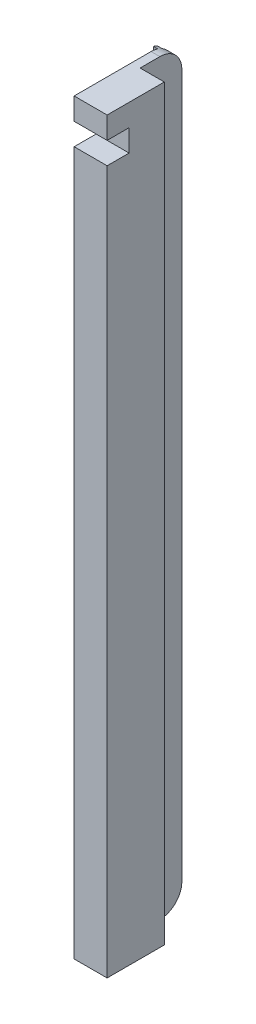
SolidWorks part; units mm, degrees
ref_plane "정면" through (0, 0, 0) normal (0, 0, 1) x (1, 0, 0)
ref_plane "윗면" through (0, 0, 0) normal (0, 1, 0) x (1, 0, 0)
ref_plane "우측면" through (0, 0, 0) normal (1, 0, 0) x (0, 0, -1)
sketch "스케치1" plane through (0, 0, 0) normal (0, 0, 1) x (1, 0, 0)
  line L0 (-318.5049, 0) -> (318.5049, 0) construction
  line L1 (0, 0) -> (0, -258.8265) construction
  line L2 (-168, 0) -> (168, 0)
  line L3 (-168, -20) -> (168, -20)
  line L4 (168, -20) -> (168, 0) construction
  line L5 (168, -20) -> (168, -340)
  line L6 (172, -340) -> (172, 0)
  line L7 (168, 0) -> (183, 0)
  line L8 (183, 0) -> (183, -340)
  line L9 (183, -340) -> (168, -340)
  line L10 (-168, -20) -> (-168, 0) construction
  line L11 (-183, -340) -> (-168, -340)
  line L12 (-183, 0) -> (-183, -340)
  line L13 (-168, 0) -> (-183, 0)
  line L14 (-172, -340) -> (-172, 0)
  line L15 (-168, -20) -> (-168, -340)
  line L16 (168, -20) -> (168, 0)
  line L17 (-168, -20) -> (-168, 0)
  point P14 (0, -20)
  dimension "D1" = 168
  dimension "D2" = 20
  dimension "D3" = 4
  dimension "D4" = 340
  dimension "D5" = 15
extrude "보스-돌출1" add sketch "스케치1" along normal blind 26 contours L3 L5 L9 L8 L7 L2 L13 L12 L11 L15
extrude "보스-돌출2" add sketch "스케치1<4>" against normal blind 19 contours L16 L5 L9 L6 L7 | L15 L17 L13 L14 L11 region at (-170, -170, 0) region at (170, -170, 0)
sketch "스케치1<4>" plane through (0, 0, 0) normal (0, 0, 1) x (1, 0, 0) same geometry as "스케치1"
fillet "필렛1" radius 10 4 edges at (-170, 0, -19) (170, 0, -19) (170, -340, -19) (-170, -340, -19)
sketch "스케치2" plane through (172, 0, 0) normal (1, 0, 0) x (0, 0, -1)
  line L0 (14, -340) -> (14, 0)
  line L1 (12, 0) -> (12, -340)
  line L4 (19, -330) -> (19, -10)
  line L5 (9, 0) -> (0, 0)
  line L6 (0, 0) -> (0, -340)
  line L7 (0, -340) -> (9, -340)
  line L8 (19, -330) -> (19, -10)
  line L9 (9, 0) -> (0, 0)
  line L10 (0, 0) -> (0, -340)
  line L11 (0, -340) -> (9, -340)
  arc A2 (19, -10) -> (9, 0) centre (9, -10) ccw
  arc A3 (9, -340) -> (19, -330) centre (9, -330) ccw
  arc A4 (19, -10) -> (9, 0) centre (9, -10) ccw
  arc A5 (9, -340) -> (19, -330) centre (9, -330) ccw
  dimension "D2" = 5
  dimension "D3" = 2
  dimension "D1" = 0
sketch "스케치3" plane through (168, 0, 0) normal (-1, 0, 0) x (0, 0, 1)
  line L0 (-12, 0) -> (-12, -340) construction
  line L1 (-14, -340) -> (-14, 0) construction
  line L2 (-12, 0) -> (-12, -340)
  line L3 (-14, -340) -> (-14, 0)
  line L4 (-19, -10) -> (-19, -330)
  line L5 (0, 0) -> (-9, 0)
  line L6 (0, -340) -> (0, 0)
  line L7 (-9, -340) -> (0, -340)
  line L8 (-19, -10) -> (-19, -330)
  line L9 (0, 0) -> (-9, 0)
  line L10 (0, -340) -> (0, 0)
  line L11 (-9, -340) -> (0, -340)
  arc A2 (-9, 0) -> (-19, -10) centre (-9, -10) ccw
  arc A3 (-19, -330) -> (-9, -340) centre (-9, -330) ccw
  arc A4 (-9, 0) -> (-19, -10) centre (-9, -10) ccw
  arc A5 (-19, -330) -> (-9, -340) centre (-9, -330) ccw
  arc M8 (-9, 0) -> (-19, -10) centre (-9, -10) ccw
  arc M10 (-19, -330) -> (-9, -340) centre (-9, -330) ccw
  dimension "D1" = 0
extrude "보스-돌출3" add sketch "스케치3" along normal blind 2 contours L3 L2 M10 M8 region at (168, -170, -12.9991)
mirror "대칭 복사1" about plane through (0, 0, 0) normal (1, 0, 0) of "보스-돌출3"
sketch "스케치5" plane through (0, 0, 0) normal (0, 1, 0) x (1, 0, 0)
  line L0 (-7, 0) -> (-7, -26)
  line L1 (7, 0) -> (7, -26)
  line L2 (-168, 0) -> (-168, -6)
  line L3 (-168, -6) -> (-7, -6)
  line L4 (7, -6) -> (168, -6)
  line L5 (168, -6) -> (168, 0)
  line L12 (-168, 0) -> (-168, 9)
  line L13 (-168, 9) -> (-172, 9)
  line L14 (-172, 9) -> (-172, 0)
  line L15 (-172, 0) -> (-183, 0)
  line L16 (-183, 0) -> (-183, -26)
  line L17 (-183, -26) -> (183, -26)
  line L18 (183, -26) -> (183, 0)
  line L19 (183, 0) -> (172, 0)
  line L20 (172, 0) -> (172, 9)
  line L21 (172, 9) -> (168, 9)
  line L22 (168, 9) -> (168, 0)
  line L23 (168, 0) -> (-168, 0)
  line L24 (-168, 0) -> (-168, 9)
  line L25 (-168, 9) -> (-172, 9)
  line L26 (-172, 9) -> (-172, 0)
  line L27 (-172, 0) -> (-183, 0)
  line L28 (-183, 0) -> (-183, -26)
  line L29 (-183, -26) -> (183, -26)
  line L30 (183, -26) -> (183, 0)
  line L31 (183, 0) -> (172, 0)
  line L32 (172, 0) -> (172, 9)
  line L33 (172, 9) -> (168, 9)
  line L34 (168, 9) -> (168, 0)
  line L35 (168, 0) -> (-168, 0)
  line M27 (168, 0) -> (-168, 0)
  dimension "D2" = 7
  dimension "D3" = 7
  dimension "D4" = 6
  dimension "D1" = 0
extrude "컷-돌출1" cut sketch "스케치5" against normal blind 52 contours L2 L3 L0 M27 | L4 L5 L1 M27 region at (-87.5, 0, 3) region at (87.5, 0, 3)
sketch "스케치6" plane through (168, 0, 0) normal (-1, 0, 0) x (0, 0, 1)
  line L0 (26, -20) -> (26, -340) construction
  line L1 (-71.7494, 105.886) -> (84.6976, 105.886)
  line L2 (-71.7494, 105.886) -> (-71.7494, -374.2228)
  line L3 (-71.7494, -374.2228) -> (84.6976, -374.2228)
  line L4 (84.6976, 105.886) -> (84.6976, -374.2228)
  line L5 (-71.7494, 105.886) -> (84.6976, -374.2228) construction
  line L6 (-71.7494, -374.2228) -> (84.6976, 105.886) construction
  line L7 (26, -340) -> (0, -340) construction
  line L8 (26, 0) -> (6, 0)
  line L9 (-9, 0) -> (6, 0)
  line L10 (-9, 0) -> (6, 0)
  line L11 (26, 0) -> (6, 0)
  line L12 (26, -20) -> (26, -340)
  line L13 (26, -20) -> (26, 0)
  line L14 (26, -20) -> (26, 0)
  line L15 (26, -20) -> (26, -340)
  line L16 (26, -20) -> (6, -20)
  line L17 (26, -20) -> (6, -20)
  line L18 (6, -20) -> (6, 0)
  line L19 (6, -20) -> (6, 0)
  point P0 (6.4741, -134.1684)
  line M5 (26, -20) -> (6, -20)
  line M6 (6, -20) -> (6, 0)
  line M7 (6, 0) -> (-9, 0)
  arc M8 (-9, 0) -> (-12, -0.4606) centre (-9, -10) ccw
  line M9 (-12, -0.4606) -> (-12, -339.5394)
  arc M10 (-12, -339.5394) -> (-9, -340) centre (-9, -330) ccw
  line M11 (-9, -340) -> (26, -340)
  line M12 (26, -340) -> (26, -20)
  dimension "D1" = 19.5259
  dimension "D2" = 240.0544
  dimension "D3" = 156.447
  dimension "D4" = 205.8316
extrude "컷-돌출3" cut sketch "스케치6" along normal blind 401 contours L4 L1 L2 L3 L14 L11 M12 M11 M10 M9 M8 M7 | L14 L11 M5 M6 | M12 M5 M6 M7 M8 M9 M10 M11 region at (168, 100.8364, 6.4741) region at (168, -10, 16) region at (168, -175.1122, 6.7138)
sketch "스케치7" plane through (168, 0, 0) normal (-1, 0, 0) x (0, 0, 1)
  line L0 (26, -20) -> (26, -340) construction
  line L1 (26, 0) -> (6, 0) construction
  line L2 (26, -20) -> (26, 0) construction
  line L3 (26, -20) -> (6, -20) construction
  line L4 (26, -340) -> (26, 0)
  line L5 (26, 0) -> (-9, 0)
  line L6 (-19, -10) -> (-19, -330)
  line L7 (-9, -340) -> (26, -340)
  line L8 (26, -340) -> (26, 0)
  line L9 (26, 0) -> (-9, 0)
  line L10 (-19, -10) -> (-19, -330)
  line L11 (-9, -340) -> (26, -340)
  line L12 (6, -20) -> (6, 0) construction
  line L13 (-9, 0) -> (6, 0) construction
  line L14 (-71.7494, 105.886) -> (84.6976, 105.886) construction
  line L15 (84.6976, 105.886) -> (84.6976, -374.2228) construction
  line L16 (-71.7494, -374.2228) -> (84.6976, -374.2228) construction
  line L17 (-71.7494, 105.886) -> (-71.7494, -374.2228) construction
  line L18 (26, -20) -> (26, -340)
  line L19 (26, 0) -> (6, 0)
  line L20 (26, -20) -> (26, 0)
  line L21 (26, -20) -> (6, -20)
  line L22 (6, -20) -> (6, 0)
  line L23 (-9, 0) -> (6, 0)
  line L24 (-71.7494, 105.886) -> (84.6976, 105.886)
  line L25 (84.6976, 105.886) -> (84.6976, -374.2228)
  line L26 (-71.7494, -374.2228) -> (84.6976, -374.2228)
  line L27 (-71.7494, 105.886) -> (-71.7494, -374.2228)
  line L29 (16, -10) -> (26, -10)
  line L30 (16, -10) -> (16, -20)
  line L31 (16, -20) -> (26, -20)
  line L32 (26, -10) -> (26, -20)
  line L33 (16, -10) -> (26, -20) construction
  line L34 (16, -20) -> (26, -10) construction
  arc A2 (-9, 0) -> (-19, -10) centre (-9, -10) ccw
  arc A3 (-19, -330) -> (-9, -340) centre (-9, -330) ccw
  arc A4 (-9, 0) -> (-19, -10) centre (-9, -10) ccw
  arc A5 (-19, -330) -> (-9, -340) centre (-9, -330) ccw
  point P15 (21, -15)
  dimension "D2" = 10
  dimension "D3" = 10
  dimension "D4" = 0
  dimension "D1" = 0
extrude "컷-돌출4" cut sketch "스케치7" against normal blind 401 contours L29 L30 L21 L8 region at (168, -15, 21)
sketch "스케치8" plane through (168, 0, 0) normal (-1, 0, 0) x (0, 0, 1)
  line L0 (8.5, 0) -> (8.5, -340) construction
  line L1 (-9, 0) -> (26, 0) construction
  line L2 (26, -340) -> (-9, -340) construction
  line L3 (17.4937, -170) -> (26, -170)
  line L4 (6.3875, -171) -> (-14, -171)
  line L5 (7.5063, -170) -> (-14, -170)
  line L6 (17.6188, -172.1118) -> (18.3686, -178.7764)
  line L7 (16.5, -171.1118) -> (17.3749, -178.8882)
  line L8 (16.3812, -180) -> (8.6188, -180)
  line L9 (7.6251, -178.8882) -> (8.5, -171.1118)
  line L10 (16.3812, -181) -> (8.6188, -181)
  line L11 (6.6314, -178.7764) -> (7.3812, -172.1118)
  line L12 (18.6125, -171) -> (26, -171)
  line L13 (6.6314, -178.7764) -> (7.5063, -171) construction
  line L14 (7.5063, -171) -> (-14, -171) construction
  line L15 (16, -10) -> (26, -10)
  line L16 (26, -10) -> (26, 0)
  line L17 (26, 0) -> (-9, 0)
  line L18 (-19, -10) -> (-19, -330)
  line L19 (-9, -340) -> (26, -340)
  line L20 (26, -340) -> (26, -20)
  line L21 (26, -20) -> (16, -20)
  line L22 (16, -20) -> (16, -10)
  line L23 (16, -10) -> (26, -10)
  line L24 (26, -10) -> (26, 0)
  line L25 (26, 0) -> (-9, 0)
  line L26 (-19, -10) -> (-19, -165)
  line L27 (-9, -340) -> (26, -340)
  line L28 (26, -340) -> (26, -20)
  line L29 (26, -20) -> (16, -20)
  line L30 (16, -20) -> (16, -10)
  line L31 (17.4937, -171) -> (26, -171) construction
  line L32 (17.4937, -171) -> (18.3686, -178.7764) construction
  line L33 (-14, -171) -> (-19, -171)
  line L34 (-19, -330) -> (-19, -10) construction
  line L35 (-19, -330) -> (-19, -10)
  line L36 (-19, -330) -> (-19, -172.4162)
  line L37 (-19, -171) -> (-19, -330)
  arc A0 (-19, -165) -> (-14, -170) centre (-14, -165) ccw
  arc A1 (7.5063, -170) -> (8.5, -171.1118) centre (7.5063, -171) cw
  arc A2 (-9, 0) -> (-19, -10) centre (-9, -10) ccw
  arc A3 (-19, -330) -> (-9, -340) centre (-9, -330) ccw
  arc A4 (-9, 0) -> (-19, -10) centre (-9, -10) ccw
  arc A5 (-19, -330) -> (-9, -340) centre (-9, -330) ccw
  arc A6 (17.4937, -170) -> (16.5, -171.1118) centre (17.4937, -171) ccw
  arc A7 (8.6188, -180) -> (7.6251, -178.8882) centre (8.6188, -179) cw
  arc A8 (16.3812, -180) -> (17.3749, -178.8882) centre (16.3812, -179) ccw
  arc A9 (-16.25, -170.5621) -> (-14, -171) centre (-14, -165) ccw
  arc A10 (16.3812, -181) -> (18.3686, -178.7764) centre (16.3812, -179) ccw
  arc A11 (8.6188, -181) -> (6.6314, -178.7764) centre (8.6188, -179) cw
  arc A12 (7.3812, -172.1118) -> (6.3875, -171) centre (6.3875, -172) ccw
  arc A13 (18.6125, -171) -> (17.6188, -172.1118) centre (18.6125, -172) ccw
  arc A14 (-20, -165) -> (-14, -171) centre (-14, -165) ccw construction
  arc A15 (-19, -172.4162) -> (-16.25, -170.5621) centre (-17, -172.4162) cw
  point P11 (8.5, -170)
  point P36 (7.5, -180)
  point P39 (17.5, -180)
  dimension "D2" = 5
  dimension "D3" = 1
  dimension "D9" = 1
  dimension "D13" = 1
  dimension "D14" = 2
  dimension "D4" = 10
  dimension "D5" = 8
  dimension "D6" = 10
  dimension "D7" = 1
  dimension "D8" = 8
  dimension "D1" = 0
  dimension "D10" = 1
  dimension "D11" = 1
  dimension "D12" = 1
sketch "스케치9" plane through (168, 0, 0) normal (-1, 0, 0) x (0, 0, 1)
  line L0 (-14, -340) -> (-14, 0) construction
  line L1 (-14, -340) -> (-14, 0)
  line L2 (-12, 0) -> (-12, -340) construction
  line L3 (-12, 0) -> (-12, -340)
  line L8 (16, -10) -> (26, -10)
  line L9 (26, -10) -> (26, 0)
  line L10 (26, 0) -> (-9, 0)
  line L11 (-19, -10) -> (-19, -330)
  line L12 (-9, -340) -> (26, -340)
  line L13 (26, -340) -> (26, -20)
  line L14 (26, -20) -> (16, -20)
  line L15 (16, -20) -> (16, -10)
  line L16 (16, -10) -> (26, -10)
  line L17 (26, -10) -> (26, 0)
  line L18 (26, 0) -> (-9, 0)
  line L19 (-19, -10) -> (-19, -330)
  line L20 (-9, -340) -> (26, -340)
  line L21 (26, -340) -> (26, -20)
  line L22 (26, -20) -> (16, -20)
  line L23 (16, -20) -> (16, -10)
  arc A2 (-9, 0) -> (-19, -10) centre (-9, -10) ccw
  arc A3 (-19, -330) -> (-9, -340) centre (-9, -330) ccw
  arc A4 (-9, 0) -> (-19, -10) centre (-9, -10) ccw
  arc A5 (-19, -330) -> (-9, -340) centre (-9, -330) ccw
  arc M14 (-9, 0) -> (-19, -10) centre (-9, -10) ccw
  arc M16 (-19, -330) -> (-9, -340) centre (-9, -330) ccw
  dimension "D1" = 0
extrude "보스-돌출4" add sketch "스케치9" along normal blind 2 contours L3 L1 M14 M16 region at (168, -170, -12.9991)
